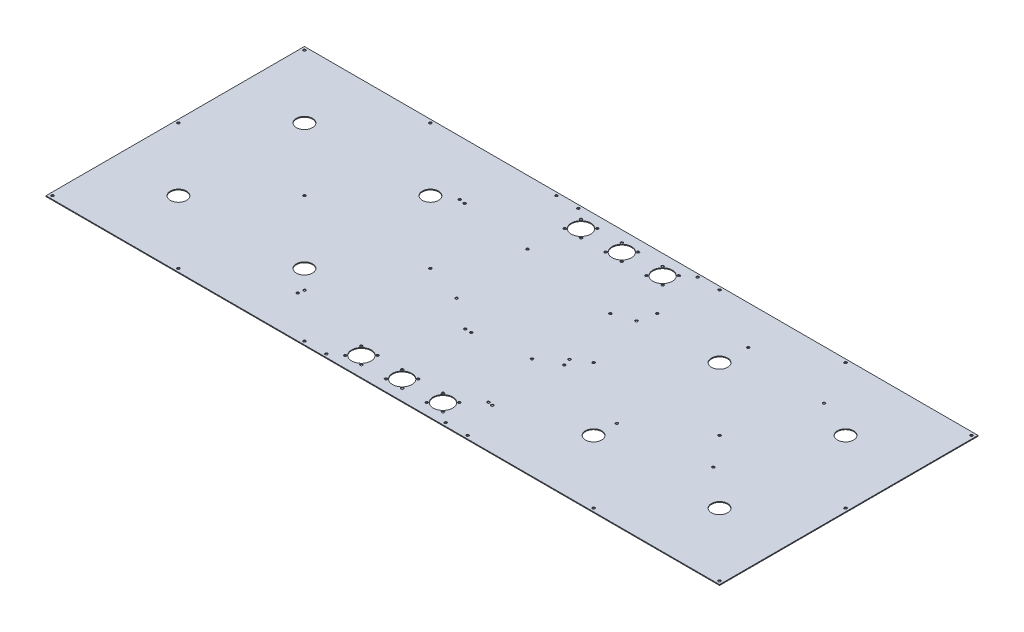
SolidWorks part; units mm, degrees
ref_plane "Front Plane" through (0, 0, 0) normal (0, 0, 1) x (1, 0, 0)
ref_plane "Top Plane" through (0, 0, 0) normal (0, 1, 0) x (1, 0, 0)
ref_plane "Right Plane" through (0, 0, 0) normal (1, 0, 0) x (0, 0, -1)
sketch "main_plate" plane through (0, 0, 0) normal (0, 1, 0) x (1, 0, 0)
  line L1 (-417, 160) -> (417, 160)
  line L2 (-417, 160) -> (-417, -160)
  line L3 (-417, -160) -> (417, -160)
  line L4 (417, 160) -> (417, -160)
  line L5 (-417, 160) -> (417, -160) construction
  line L6 (-417, -160) -> (417, 160) construction
  point P0 (0, 0)
  dimension "D1" = 320
  dimension "D2" = 834
extrude "Boss-Extrude1" add sketch "main_plate" along normal blind 1.016
sketch "main_holes" plane through (0, 1.016, 0) normal (0, 1, 0) x (1, 0, 0)
  line L0 (-417, 160) -> (-417, -160) construction
  line L1 (417, 160) -> (-417, 160) construction
  line L2 (-417, 0) -> (417, 0) construction
  line L3 (417, -160) -> (417, 160) construction
  line L4 (-417, -160) -> (417, -160) construction
  line L5 (0, 160) -> (0, -160) construction
  circle A0 centre (-413, 156) radius 1.6
  circle A6 centre (-257, 156) radius 1.6
  circle A7 centre (-101, 156) radius 1.6
  circle A8 centre (-257, 0) radius 1.6
  circle A9 centre (-101, 0) radius 1.6
  circle A10 centre (-257, -156) radius 1.6
  circle A11 centre (-101, -156) radius 1.6
  circle A12 centre (-413, 0) radius 1.6
  circle A13 centre (-413, -156) radius 1.6
  circle A18 centre (413, -156) radius 1.6
  circle A19 centre (413, 0) radius 1.6
  circle A20 centre (101, -156) radius 1.6
  circle A21 centre (257, -156) radius 1.6
  circle A22 centre (101, 0) radius 1.6
  circle A23 centre (257, 0) radius 1.6
  circle A24 centre (101, 156) radius 1.6
  circle A25 centre (257, 156) radius 1.6
  circle A28 centre (413, 156) radius 1.6
  circle A29 centre (-73.8188, 156) radius 1.6
  circle A31 centre (73.8188, 156) radius 1.6
  circle A32 centre (73.8188, -156) radius 1.6
  circle A33 centre (-73.8188, -156) radius 1.6
  dimension "D3" = 3.2
  dimension "D1" = 4
  dimension "D2" = 4
  dimension "D4" = 3
  dimension "D5" = 3
  dimension "D6" = 73.8188
extrude "Cut-Extrude1" cut sketch "main_holes" against normal through all
sketch "sma" plane through (0, 1.016, 0) normal (0, 1, 0) x (1, 0, 0)
  line L0 (0, 160) -> (0, -160) construction
  line L1 (417, 160) -> (-417, 160) construction
  line L2 (-417, -160) -> (417, -160) construction
  line L3 (-413, 156) -> (-257, 156) construction
  line L7 (-257, 0) -> (-413, 0) construction
  line L8 (-413, 0) -> (-413, 156) construction
  line L9 (-257, 156) -> (-257, 0) construction
  circle A0 centre (-335, 78) radius 10
  circle A1 centre (-179, 78) radius 10
  circle A2 centre (-179, -78) radius 10
  circle A3 centre (-335, -78) radius 10
  circle A4 centre (335, 78) radius 10
  circle A5 centre (179, 78) radius 10
  circle A6 centre (335, -78) radius 10
  circle A7 centre (179, -78) radius 10
  point P9 (-413, 78)
  point P10 (-335, 156)
  dimension "D1" = 20
  dimension "D2" = 2
  dimension "D3" = 2
extrude "Cut-Extrude2" cut sketch "sma" against normal through all
sketch "ads9+eval"
sketch_block_instance "Block9-1"
sketch_block "Block9"
sketch_block_instance "Block8-8"
sketch_block "Block8" parameters "D6"=3.2, "D1"=217.932, "D2"=70.358, "D3"=61.468, "D4"=193.04, "D5"=18.796, "D7"=81.28, "D8"=68.58, "D9"=94.71, "D10"=106.68
sketch_block_instance "Block7-4"
sketch_block "Block7" parameters "D3"=3.2, "D1"=215.9, "D2"=259.71, "D4"=6.48, "D5"=7.24, "D6"=111, "D7"=103.38, "D8"=18.04, "D9"=12.3976, "D10"=37.52, "D11"=11.13, "D12"=13.84, "D13"=110.43, "D14"=101.73, "D15"=7.74, "D16"=6.47, "D17"=37.51, "D18"=13.68, "D19"=8.76, "D20"=15.4, "D21"=8.22, "D22"=100.94, "D23"=7.02, "D24"=8.34, "D25"=18.41, "D26"=36.31, "D27"=27.78, "D28"=7.02, "D29"=8.22, "D30"=9.18, "D31"=73.31, "D32"=73.31, "D33"=82.56, "D34"=105.32, "D35"=95.85
extrude "selective_holes" [suppressed] cut sketch "ads9+eval" against normal through all
sketch "ads9+eval_2" plane through (0, 1.016, 1.016) normal (0, 1, 0) x (1, 0, 0)
  line B0 (-163.2752, -115.6705) -> (96.4348, -115.6705) construction
  line B1 (96.4348, 100.2295) -> (96.4348, -115.6705) construction
  line B2 (67.1184, 66.8966) -> (67.1184, -3.4614) construction
  line B3 (-163.2752, -115.6705) -> (96.4348, 100.2295) construction
  line B4 (85.9144, 128.1106) -> (303.8464, -64.9294) construction
  line B5 (67.1184, 31.7176) -> (303.8464, 31.5906) construction
  circle B6 centre (180.6244, 112.9368) radius 1.6
  circle B7 centre (287.3044, 100.1795) radius 1.6
  circle B8 centre (287.2308, -36.9805) radius 1.6
  circle B9 centre (180.5372, -49.6232) radius 1.6
  circle B10 centre (-156.7952, 93.2095) radius 1.6
  circle B11 centre (-149.5552, 91.8895) radius 1.6
  circle B12 centre (-155.5352, -100.2705) radius 1.6
  circle B13 centre (-156.8052, -107.4505) radius 1.6
  circle B14 centre (-14.5652, -42.3605) radius 1.6
  circle B15 centre (-6.9452, -42.3605) radius 1.6
  circle B16 centre (58.9148, -33.1105) radius 1.6
  circle B17 centre (-52.8452, -14.7305) radius 1.6
  circle B18 centre (85.3048, -19.8205) radius 1.6
  circle B19 centre (82.5948, -10.3505) radius 1.6
  circle B20 centre (78.3948, -106.4905) radius 1.6
  circle B21 centre (84.0372, -107.4505) radius 1.6
  circle B22 centre (58.9248, 63.9195) radius 1.6
  circle B23 centre (82.7548, 72.4495) radius 1.6
  circle B24 centre (87.6748, 93.2095) radius 1.6
  circle B25 centre (-61.5452, 81.8195) radius 1.6
  line B26 (85.9144, 128.1106) -> (303.8464, 128.1106) construction
  line B27 (85.9144, 128.1106) -> (85.9144, 66.8966) construction
  line B28 (85.9144, -64.9294) -> (303.8464, -64.9294) construction
  line B29 (303.8464, 128.1106) -> (303.8464, -64.9294) construction
  line B30 (85.9144, -64.9294) -> (303.8464, 128.1106) construction
  line B31 (67.1184, 66.8966) -> (85.9144, 66.8966) construction
  line B32 (67.1184, -3.4614) -> (85.9144, -3.4614) construction
  line B33 (85.9144, -64.9294) -> (85.9144, -3.4614) construction
  line B34 (-163.2752, 100.2295) -> (96.4348, 100.2295) construction
  line B35 (-163.2752, 100.2295) -> (-163.2752, -115.6705) construction
  line B36 (-163.2752, 100.2295) -> (96.4348, -115.6705) construction
sketch_block_instance "Block9-2"
extrude "full_holes" cut sketch "ads9+eval_2" against normal through all
sketch "fan" plane through (0, 1.016, -2.032) normal (0, -1, 0) x (1, 0, 0)
  line L0 (417, -157.968) -> (-417, -157.968) construction
  line L1 (-417, 162.032) -> (417, 162.032) construction
  point P2 (0, 144.8519)
  point P3 (-161.9134, 199.2318)
  point P4 (0, -137.9511)
  point P5 (0, 140.2808)
  point P6 (0, 0)
  point P7 (-20.486, 141.4815)
  point P10 (0, 137.9455)
  point P11 (-48.6845, -110.8414)
  point P12 (9.1106, -110.8414)
  circle B0 centre (-10, -123.968) radius 1.6
  circle B1 centre (10, -123.968) radius 1.6
  circle B2 centre (10, -143.968) radius 1.6
  circle B3 centre (-10, -143.968) radius 1.6
  circle B4 centre (0, -133.968) radius 12
  circle B5 centre (-60.5, -123.968) radius 1.6
  circle B6 centre (-40.5, -123.968) radius 1.6
  circle B7 centre (-40.5, -143.968) radius 1.6
  circle B8 centre (-60.5, -143.968) radius 1.6
  circle B9 centre (-50.5, -133.968) radius 12
  circle B10 centre (40.5, -123.968) radius 1.6
  circle B11 centre (60.5, -123.968) radius 1.6
  circle B12 centre (60.5, -143.968) radius 1.6
  circle B13 centre (40.5, -143.968) radius 1.6
  circle B14 centre (50.5, -133.968) radius 12
  circle B15 centre (-10, -144.984) radius 1.6
  circle B16 centre (10, -144.984) radius 1.6
  circle B17 centre (10, -164.984) radius 1.6
  circle B18 centre (-10, -164.984) radius 1.6
  circle B19 centre (0, -154.984) radius 12
  circle B20 centre (-10, 148.032) radius 1.6
  circle B21 centre (10, 148.032) radius 1.6
  circle B22 centre (10, 128.032) radius 1.6
  circle B23 centre (-10, 128.032) radius 1.6
  circle B24 centre (0, 138.032) radius 12
  circle B25 centre (-60.5, 148.032) radius 1.6
  circle B26 centre (-40.5, 148.032) radius 1.6
  circle B27 centre (-40.5, 128.032) radius 1.6
  circle B28 centre (-60.5, 128.032) radius 1.6
  circle B29 centre (-50.5, 138.032) radius 12
  circle B30 centre (40.5, 148.032) radius 1.6
  circle B31 centre (60.5, 148.032) radius 1.6
  circle B32 centre (60.5, 128.032) radius 1.6
  circle B33 centre (40.5, 128.032) radius 1.6
  circle B34 centre (50.5, 138.032) radius 12
  dimension "D1" = 24
  dimension "D2" = 24
sketch_block_instance "Block13-1"
sketch_block "Block13"
sketch_block_instance "Block2-13"
sketch_block "Block2" parameters "D1"=3.2, "D2"=24, "D3"=10, "D4"=10, "D5"=10, "D6"=10
sketch_block_instance "Block2-14"
sketch_block_instance "Block2-15"
sketch_block_instance "Block2-16"
sketch_block_instance "Block13-2"
extrude "Cut-Extrude4" cut sketch "fan" along normal through all
